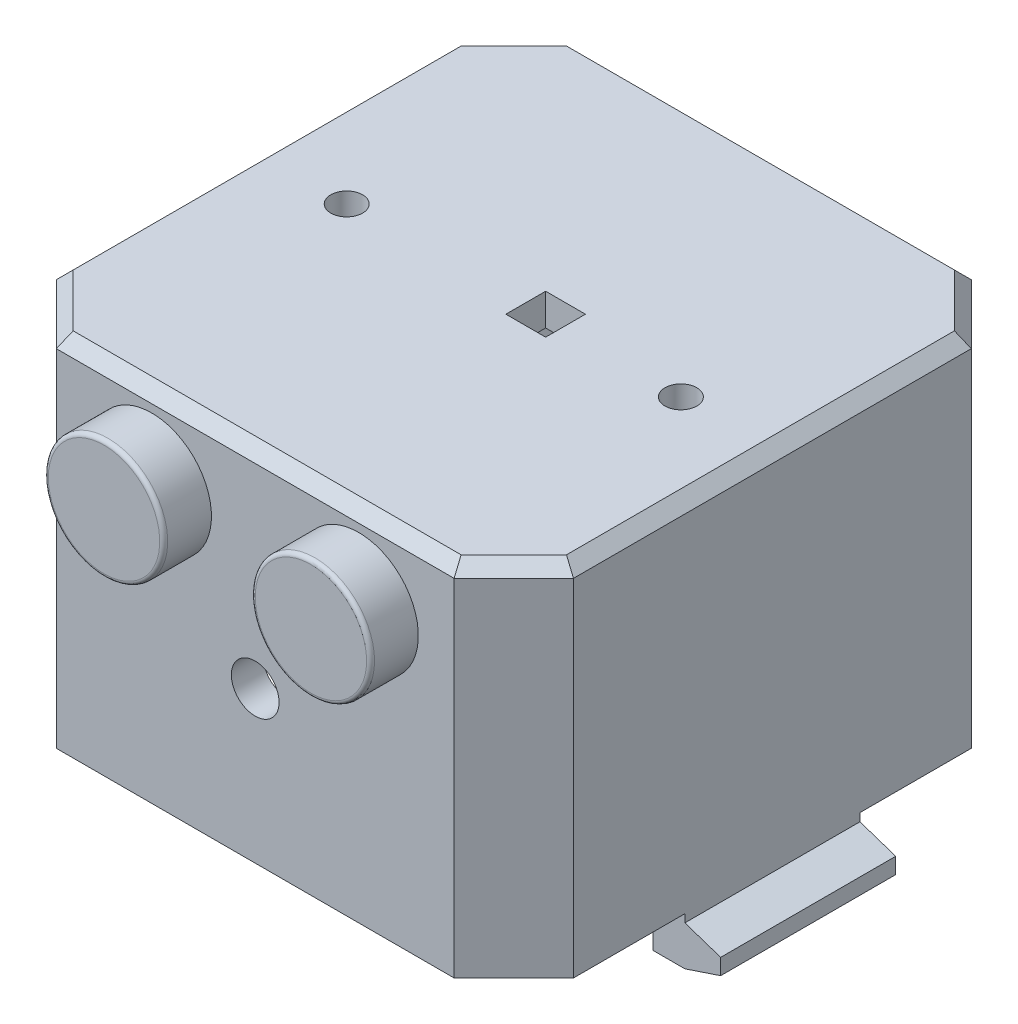
SolidWorks part; units mm, degrees
ref_plane "Alzado" through (0, 0, 0) normal (0, 0, 1) x (1, 0, 0)
ref_plane "Planta" through (0, 0, 0) normal (0, 1, 0) x (1, 0, 0)
ref_plane "Vista lateral" through (0, 0, 0) normal (1, 0, 0) x (0, 0, -1)
sketch "Croquis1" plane through (0, 0, 0) normal (0, 1, 0) x (1, 0, 0)
  line L1 (-25, -32.5) -> (25, -32.5)
  line L3 (-25, 32.5) -> (25, 32.5)
  line L5 (-25, -32.5) -> (25, 32.5) construction
  line L6 (-25, 32.5) -> (25, -32.5) construction
  line L10 (32.5, 25) -> (32.5, -25)
  line L11 (25, -32.5) -> (32.5, -25)
  line L12 (32.5, 25) -> (25, 32.5)
  line L13 (-32.5, 25) -> (-32.5, -25)
  line L14 (-32.5, -25) -> (-25, -32.5)
  line L15 (-32.5, 25) -> (-25, 32.5)
  point P0 (0, 0)
  point P10 (0, 32.5)
  dimension "D1" = 65
  dimension "D2" = 65
  dimension "D3" = 50
  dimension "D4" = 50
  dimension "D5" = 25
  dimension "D6" = 25
extrude "Saliente-Extruir1" add sketch "Croquis1" along normal blind 45
shell "Vaciado2" thickness 4 removed face at (0, 0, 0)
chamfer "Chaflán3" distance 1.5 angle 45 8 edges at (0, 45, -32.5) (32.5, 45, 0) (0, 45, 32.5) (-32.5, 45, 0) (-28.75, 45, 28.75) (28.75, 45, 28.75) (28.75, 45, -28.75) (-28.75, 45, -28.75)
sketch "Croquis2" plane through (0, 0, 32.5) normal (0, 0, 1) x (1, 0, 0)
  line L0 (0, 0) -> (0, 6.916) construction
  circle A0 centre (13, 35) radius 7.5
  circle A1 centre (-13, 35) radius 7.5
  dimension "D1" = 15
  dimension "D2" = 13
  dimension "D3" = 35
extrude "Saliente-Extruir2" add sketch "Croquis2" along normal blind 6
sketch "Croquis4" plane through (0, 0, 28.5) normal (0, 0, -1) x (-1, 0, 0)
  line L0 (0, 0) -> (0, 4.7403) construction
  line L1 (0, 0) -> (0, 6.916) construction
  circle A0 centre (-13, 35) radius 5
  circle A1 centre (13, 35) radius 5
  dimension "D1" = 10
extrude "Cortar-Extruir2" cut sketch "Croquis4" against normal blind 8
fillet "Redondeo1" radius 0.5 2 edges at (-20.5, 35, 38.5) (20.5, 35, 38.5)
sketch "Croquis5" plane through (0, 0, 32.5) normal (0, 0, 1) x (1, 0, 0)
  circle A0 centre (0, 19) radius 3
  dimension "D2" = 6
  dimension "D1" = 19
extrude "Cortar-Extruir3" cut sketch "Croquis5" against normal blind 10
sketch "Croquis13" plane through (0, 0, 36.5) normal (0, 0, -1) x (-1, 0, 0)
  circle A0 centre (-13, 35) radius 2.6
  circle A1 centre (13, 35) radius 2.6
  circle A2 centre (13, 35) radius 5
  circle A3 centre (-13, 35) radius 5
  dimension "D1" = 5.2
  dimension "D2" = 5.2
extrude "Saliente-Extruir8" add sketch "Croquis13" along normal blind 8
sketch "Croquis7" plane through (0, 0, 28.5) normal (0, 0, -1) x (-1, 0, 0)
  line L0 (23.3431, 0) -> (-23.3431, 0) construction
  line L1 (-14.08, 8) -> (-9.08, 8)
  line L2 (-14.08, 8) -> (-14.08, 13)
  line L3 (-14.08, 13) -> (-9.08, 13)
  line L4 (-9.08, 8) -> (-9.08, 13)
  line L5 (-14.08, 8) -> (-9.08, 13) construction
  line L6 (-14.08, 13) -> (-9.08, 8) construction
  line L8 (-14.08, 25.5) -> (-9.08, 25.5)
  line L9 (-14.08, 25.5) -> (-14.08, 30.5)
  line L10 (-14.08, 30.5) -> (-9.08, 30.5)
  line L11 (-9.08, 25.5) -> (-9.08, 30.5)
  line L12 (-14.08, 25.5) -> (-9.08, 30.5) construction
  line L13 (-14.08, 30.5) -> (-9.08, 25.5) construction
  line L14 (13.93, 13) -> (8.93, 8) construction
  line L15 (13.93, 8) -> (8.93, 13) construction
  line L16 (8.93, 8) -> (8.93, 13)
  line L17 (13.93, 13) -> (8.93, 13)
  line L18 (13.93, 8) -> (13.93, 13)
  line L19 (13.93, 8) -> (8.93, 8)
  line L20 (13.93, 30.5) -> (8.93, 25.5) construction
  line L21 (13.93, 25.5) -> (8.93, 30.5) construction
  line L22 (8.93, 25.5) -> (8.93, 30.5)
  line L23 (13.93, 30.5) -> (8.93, 30.5)
  line L24 (13.93, 25.5) -> (13.93, 30.5)
  line L25 (13.93, 25.5) -> (8.93, 25.5)
  point P0 (-11.58, 10.5)
  point P8 (-11.58, 28)
  point P13 (0, 0)
  point P15 (11.43, 10.5)
  point P16 (11.43, 28)
  point P20 (11.43, 10.5)
  point P25 (11.43, 28)
  point P26 (-11.58, 28)
  point P27 (11.43, 28)
  point P28 (11.43, 10.5)
  point P29 (-11.58, 10.5)
  dimension "D1" = 10.5
  dimension "D2" = 5
  dimension "D3" = 5
  dimension "D4" = 11.58
  dimension "D5" = 5
  dimension "D6" = 5
  dimension "D7" = 28
  dimension "D8" = 23.01
  dimension "D9" = 23.01
  dimension "D10" = 5
  dimension "D11" = 5
  dimension "D12" = 5
  dimension "D13" = 5
  dimension "D14" = 10.5
  dimension "D15" = 28
extrude "Saliente-Extruir3" add sketch "Croquis7" along normal blind 1
sketch "Croquis8" plane through (0, 0, 27.5) normal (0, 0, -1) x (-1, 0, 0)
  line L0 (0, 0) -> (0, 4.8013) construction
  line L1 (23.3431, 0) -> (-23.3431, 0) construction
  circle A0 centre (-11.505, 10.4893) radius 2.5
  circle A1 centre (-11.505, 27.9763) radius 2.5
  circle A2 centre (11.505, 10.4893) radius 2.5
  circle A3 centre (11.505, 27.9763) radius 2.5
  dimension "D1" = 5
  dimension "D2" = 5
  dimension "D5" = 5
  dimension "D3" = 23.01
  dimension "D4" = 23.01
extrude "Saliente-Extruir4" add sketch "Croquis8" along normal blind 1
sketch "Croquis9" plane through (0, 0, 26.5) normal (0, 0, -1) x (-1, 0, 0)
  circle A0 centre (-11.505, 27.9763) radius 1.6
  circle A1 centre (-11.505, 10.4893) radius 1.6
  circle A2 centre (11.505, 10.4893) radius 1.6
  circle A3 centre (11.505, 27.9763) radius 1.6
  dimension "D1" = 3.2
  dimension "D2" = 3.2
  dimension "D3" = 3.2
  dimension "D4" = 3.2
extrude "Cortar-Extruir5" cut sketch "Croquis9" against normal blind 4
sketch "Croquis12" plane through (0, 41, 0) normal (0, -1, 0) x (1, 0, 0)
  line L0 (0, 0) -> (-5.199, 0) construction
  line L1 (-21.9, -8.93) -> (21.9, -8.93) construction
  line L2 (-21.9, -8.93) -> (-21.9, 8.93) construction
  line L3 (-21.9, 8.93) -> (21.9, 8.93) construction
  line L4 (21.9, -8.93) -> (21.9, 8.93) construction
  line L5 (-21.9, -8.93) -> (21.9, 8.93) construction
  line L6 (-21.9, 8.93) -> (21.9, -8.93) construction
  line L7 (0, 0) -> (0, 4.1573) construction
  circle A0 centre (-20.65, 7.68) radius 0.8
  circle A1 centre (-20.65, 7.68) radius 1.15
  circle A2 centre (-20.65, -7.68) radius 1.15
  circle A3 centre (-20.65, -7.68) radius 0.8
  circle A4 centre (20.65, 7.68) radius 1.15
  circle A5 centre (20.65, 7.68) radius 0.8
  circle A6 centre (20.65, -7.68) radius 1.15
  circle A7 centre (20.65, -7.68) radius 0.8
  point P0 (0, 0)
  dimension "D6" = 1.6
  dimension "D4" = 2.3
  dimension "D1" = 43.8
  dimension "D2" = 17.86
  dimension "D3" = 1.25
  dimension "D7" = 1.25
extrude "Saliente-Extruir7" add sketch "Croquis12" along normal blind 6
sketch "Croquis14" plane through (0, 41, 0) normal (0, -1, 0) x (1, 0, 0)
  line L1 (-22.15, 6.43) -> (-19.15, 6.43)
  line L2 (-22.15, 6.43) -> (-22.15, 8.93)
  line L3 (-22.15, 8.93) -> (-19.15, 8.93)
  line L4 (-19.15, 6.43) -> (-19.15, 8.93)
  line L5 (-22.15, 6.43) -> (-19.15, 8.93) construction
  line L6 (-22.15, 8.93) -> (-19.15, 6.43) construction
  line L7 (-22.15, -8.93) -> (-19.15, -8.93)
  line L8 (-22.15, -8.93) -> (-22.15, -6.43)
  line L9 (-22.15, -6.43) -> (-19.15, -6.43)
  line L10 (-19.15, -8.93) -> (-19.15, -6.43)
  line L11 (-22.15, -8.93) -> (-19.15, -6.43) construction
  line L12 (-22.15, -6.43) -> (-19.15, -8.93) construction
  line L13 (19.15, 6.43) -> (22.15, 6.43)
  line L14 (19.15, 6.43) -> (19.15, 8.93)
  line L15 (19.15, 8.93) -> (22.15, 8.93)
  line L16 (22.15, 6.43) -> (22.15, 8.93)
  line L17 (19.15, 6.43) -> (22.15, 8.93) construction
  line L18 (19.15, 8.93) -> (22.15, 6.43) construction
  line L19 (19.15, -8.93) -> (22.15, -8.93)
  line L20 (19.15, -8.93) -> (19.15, -6.43)
  line L21 (19.15, -6.43) -> (22.15, -6.43)
  line L22 (22.15, -8.93) -> (22.15, -6.43)
  line L23 (19.15, -8.93) -> (22.15, -6.43) construction
  line L24 (19.15, -6.43) -> (22.15, -8.93) construction
  point P0 (-20.65, 7.68)
  point P6 (-20.65, -7.68)
  point P12 (20.65, 7.68)
  point P18 (20.65, -7.68)
  dimension "D1" = 3
  dimension "D2" = 2.5
  dimension "D3" = 3
  dimension "D4" = 2.5
  dimension "D5" = 3
  dimension "D6" = 2.5
  dimension "D7" = 3
  dimension "D8" = 2.5
extrude "Saliente-Extruir9" add sketch "Croquis14" along normal blind 5
sketch "Croquis15" plane through (-32.5, 0, 0) normal (-1, 0, 0) x (0, 0, 1)
  line L1 (-6, 40.5) -> (6, 40.5)
  line L2 (-6, 40.5) -> (-6, 32.5)
  line L3 (-6, 32.5) -> (6, 32.5)
  line L4 (6, 40.5) -> (6, 32.5)
  dimension "D1" = 8
  dimension "D2" = 12
  dimension "D3" = 3
  dimension "D4" = 19
extrude "Cortar-Extruir6" cut sketch "Croquis15" against normal blind 7
sketch "Croquis16" plane through (0, 0, -28.5) normal (0, 0, 1) x (1, 0, 0)
  line L2 (18.95, 6.05) -> (6.55, 6.05)
  line L3 (18.95, 6.05) -> (18.95, 18.45)
  line L4 (18.95, 18.45) -> (6.55, 18.45)
  line L5 (6.55, 6.05) -> (6.55, 18.45)
  line L6 (5.5, 5) -> (20, 5)
  line L7 (5.5, 5) -> (5.5, 19.5)
  line L8 (5.5, 19.5) -> (20, 19.5)
  line L9 (20, 5) -> (20, 19.5)
  line L10 (5.5, 5) -> (20, 19.5) construction
  line L11 (5.5, 19.5) -> (20, 5) construction
  line L12 (18.95, 6.05) -> (6.55, 18.45) construction
  line L13 (18.95, 18.45) -> (6.55, 6.05) construction
  point P0 (12.75, 12.25)
  point P4 (12.75, 12.25)
  dimension "D1" = 12.4
  dimension "D2" = 12.4
  dimension "D3" = 5
  dimension "D4" = 5
  dimension "D5" = 14.5
  dimension "D6" = 14.5
extrude "Saliente-Extruir10" add sketch "Croquis16" along normal blind 3
sketch "Croquis17" plane through (0, 0, -28.5) normal (0, 0, 1) x (1, 0, 0)
  circle A0 centre (12.75, 12.25) radius 5.5
  point P4 (12.75, 12.25)
  dimension "D1" = 11
extrude "Cortar-Extruir7" cut sketch "Croquis17" against normal through all
sketch "Croquis18" plane through (0, 0, 0) normal (0, -1, 0) x (1, 0, 0)
  line L1 (-32.5, 11) -> (-28.5, 11)
  line L2 (-32.5, 11) -> (-32.5, -11)
  line L3 (-32.5, -11) -> (-28.5, -11)
  line L4 (-28.5, 11) -> (-28.5, -11)
  line L5 (-32.5, -25) -> (-32.5, 25) construction
  line L6 (0, 0) -> (0, 8.739) construction
  line L7 (28.5, 11) -> (28.5, -11)
  line L8 (32.5, -11) -> (28.5, -11)
  line L9 (32.5, 11) -> (32.5, -11)
  line L10 (32.5, 11) -> (28.5, 11)
  point P4 (-28.5, 0)
  dimension "D1" = 4
  dimension "D2" = 22
extrude "Saliente-Extruir11" add sketch "Croquis18" along normal blind 6
sketch "Croquis19" plane through (0, 0, 11) normal (0, 0, 1) x (1, 0, 0)
  line L0 (-32.5, -3.5) -> (-37, -3.5) construction
  line L1 (-37, -2.5) -> (-37, -4.5)
  line L2 (-37, -2.5) -> (-32.5, -1)
  line L3 (-32.5, -6) -> (-32.5, 0)
  line L4 (-32.5, -6) -> (-32.5, -1)
  line L5 (-32.5, -6) -> (-37, -4.5)
  line L6 (0, 0) -> (0, 6.3616) construction
  line L7 (-25, 0) -> (25, 0) construction
  line L8 (32.5, -3.5) -> (37, -3.5) construction
  line L9 (32.5, -6) -> (37, -4.5)
  line L10 (32.5, -6) -> (32.5, -1)
  line L11 (32.5, -6) -> (32.5, 0)
  line L12 (37, -2.5) -> (32.5, -1)
  line L13 (37, -2.5) -> (37, -4.5)
  point P18 (-37, -3.5)
  line M6 (-32.5, 0) -> (-32.5, -6)
  dimension "D1" = 2
extrude "Saliente-Extruir13" add sketch "Croquis19" against normal blind 22 contours L5 L2 L1 M6 | L13 L12 L10 L9 region at (-34.4286, -3.5, 11) region at (34.4286, -3.5, 11)
sketch "Croquis20" plane through (0, 45, 0) normal (0, 1, 0) x (1, 0, 0)
  line L1 (6.0029, -2) -> (1.0029, -2)
  line L2 (6.0029, -2) -> (6.0029, 3)
  line L3 (6.0029, 3) -> (1.0029, 3)
  line L4 (1.0029, -2) -> (1.0029, 3)
  dimension "D1" = 5
  dimension "D2" = 5
  dimension "D3" = 2
extrude "Cortar-Extruir8" cut sketch "Croquis20" against normal blind 10
sketch "Croquis10" plane through (0, 45, 0) normal (0, 1, 0) x (1, 0, 0)
  line L0 (-31, 24.3787) -> (-31, -24.3787) construction
  line L1 (-31, -4) -> (-11, -4) construction
  line L2 (-31, -4) -> (-31, 4) construction
  line L3 (-31, 4) -> (-11, 4) construction
  line L4 (-11, -4) -> (-11, 4) construction
  line L5 (-31, -4) -> (-11, 4) construction
  line L6 (-31, 4) -> (-11, -4) construction
  line L7 (0, 0) -> (0, 7.307) construction
  line L8 (31, 4) -> (11, -4) construction
  line L9 (31, -4) -> (11, 4) construction
  line L10 (11, -4) -> (11, 4) construction
  line L11 (31, 4) -> (11, 4) construction
  line L12 (31, -4) -> (31, 4) construction
  line L13 (31, -4) -> (11, -4) construction
  circle A0 centre (-21, 0) radius 2
  circle A1 centre (21, 0) radius 2
  point P0 (-21, 0)
  point P14 (21, 0)
  dimension "D3" = 4
  dimension "D4" = 4
  dimension "D1" = 20
  dimension "D2" = 8
extrude "Cortar-Extruir10" cut sketch "Croquis10" against normal through all
sketch "Croquis21" plane through (0, 36, 0) normal (0, -1, 0) x (1, 0, 0)
  circle A0 centre (-20.65, 7.68) radius 0.8
  circle A1 centre (20.65, 7.68) radius 0.8
  circle A2 centre (20.65, -7.68) radius 0.8
  circle A3 centre (-20.65, -7.68) radius 0.8
extrude "Cortar-Extruir11" cut sketch "Croquis21" against normal blind 5
